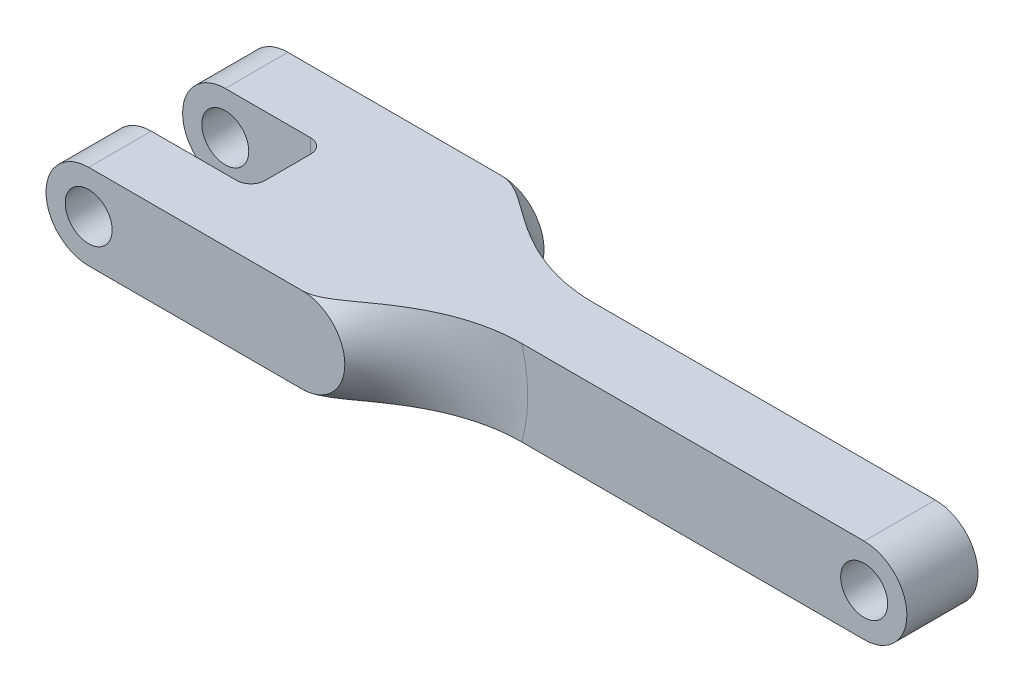
SolidWorks part; units mm, degrees
ref_plane "前视基准面" through (0, 0, 0) normal (0, 0, 1) x (1, 0, 0)
ref_plane "上视基准面" through (0, 0, 0) normal (0, 1, 0) x (1, 0, 0)
ref_plane "右视基准面" through (0, 0, 0) normal (1, 0, 0) x (0, 0, -1)
sketch "草图1" plane through (0, 0, 0) normal (0, 0, 1) x (1, 0, 0)
  line L0 (-25, 0) -> (25, 0) construction
  line L1 (-25, 3) -> (25, 3)
  line L2 (-25, -3) -> (25, -3)
  arc A0 (-25, 3) -> (-25, -3) centre (-25, 0) ccw
  arc A1 (25, -3) -> (25, 3) centre (25, 0) ccw
  circle A2 centre (-25, 0) radius 1.65
  circle A3 centre (25, 0) radius 1.65
  point P2 (0, 0)
  dimension "D2" = 3
  dimension "D3" = 3.3
  dimension "D1" = 50
extrude "凸台-拉伸1" add sketch "草图1" along normal blind 2.5 and the other way blind 2.5
sketch "草图2" plane through (0, 0, 2.5) normal (0, 0, 1) x (1, 0, 0)
  circle A0 centre (25, 0) radius 1.65 construction
  circle A1 centre (25, 0) radius 1.65 construction
  circle A2 centre (-25, 0) radius 1.65 construction
  circle A3 centre (-25, 0) radius 1.65
  circle A4 centre (-25, 0) radius 3
  circle A5 centre (-25, 0) radius 1.65 construction
  circle A6 centre (-25, 0) radius 1.65
  circle A7 centre (-25, 0) radius 3
  circle M1 centre (-25, 0) radius 1.65
  arc M2 (-25, 3) -> (-25, -3) centre (-25, 0) ccw
extrude "凸台-拉伸2" add sketch "草图2" along normal blind 4.5 and the other way blind 9.5 contours A4 M2 M1 region at (-22.9387, -2.0613, 2.5)
sketch "草图3" plane through (0, 0, 7) normal (0, 0, 1) x (1, 0, 0)
  line L0 (-25, -3) -> (25, -3) construction
  line L1 (25, 3) -> (-25, 3) construction
  line L2 (-25, -3) -> (-10, -3)
  line L3 (-10, 3) -> (-25, 3)
  circle A0 centre (-25, 0) radius 3 construction
  arc A1 (-25, -3) -> (-25, 3) centre (-25, 0) ccw
  arc A2 (-10, -3) -> (-10, 3) centre (-10, 0) ccw
  dimension "D1" = 15
extrude "凸台-拉伸3" add sketch "草图3" against normal up to surface (14 mm away) up to face at (-23.35, 0, -7)
sketch "草图4" plane through (0, 3, 0) normal (0, 1, 0) x (1, 0, 0)
  line L0 (-28, 7) -> (-28, -7) construction
  line L1 (-38, 2.6) -> (-18, 2.6)
  line L2 (-38, 2.6) -> (-38, -2.6)
  line L3 (-38, -2.6) -> (-18, -2.6)
  line L4 (-18, 2.6) -> (-18, -2.6)
  line L5 (-38, 2.6) -> (-18, -2.6) construction
  line L6 (-38, -2.6) -> (-18, 2.6) construction
  point P0 (-28, 0)
  dimension "D1" = 5.2
  dimension "D2" = 10
extrude "切除-拉伸1" cut sketch "草图4" against normal blind 13.5
fillet "圆角1" radius 10 2 edges at (-7, 0, -2.5) (-7, 0, 2.5)
fillet "圆角2" radius 1 2 edges at (-18, 0, -2.6) (-18, 0, 2.6)
